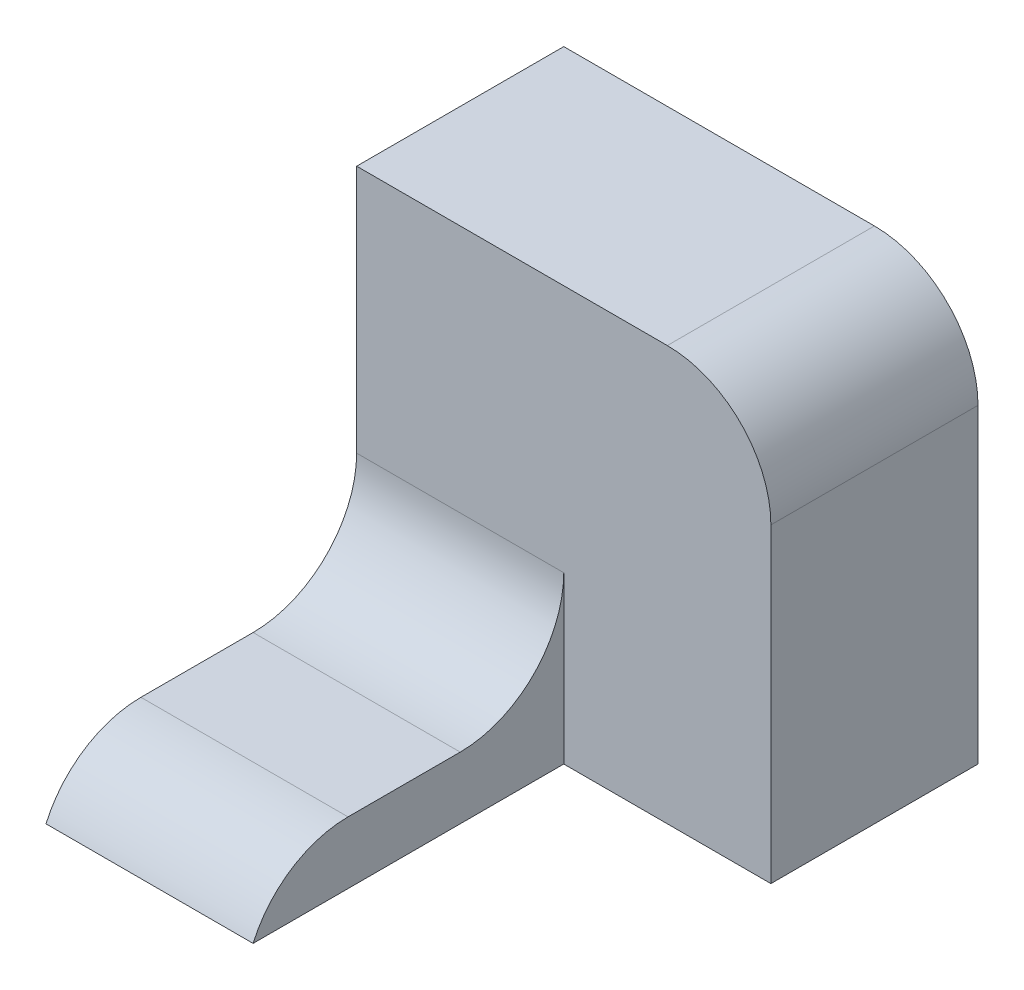
SolidWorks part; units mm, degrees
ref_plane "Front Plane" through (0, 0, 0) normal (0, 0, 1) x (1, 0, 0)
ref_plane "Top Plane" through (0, 0, 0) normal (0, 1, 0) x (1, 0, 0)
ref_plane "Right Plane" through (0, 0, 0) normal (1, 0, 0) x (0, 0, -1)
sketch "Sketch1" plane through (0, 0, 0) normal (0, 0, 1) x (1, 0, 0)
  line L1 (-30, -6) -> (-10, -6)
  line L2 (-10, -6) -> (-10, 0)
  line L3 (-10, 0) -> (-30, 0)
  line L4 (-30, 0) -> (-30, -6)
  dimension "D1" = 20
  dimension "Width" = 6
extrude "Boss-Extrude1" add sketch "Sketch1" along normal blind 30
sketch "Sketch2" plane through (0, 0, 0) normal (0, 0, 1) x (1, 0, 0)
  line L1 (-30, -6) -> (10, -6)
  line L2 (10, -6) -> (10, 34)
  line L3 (10, 34) -> (-30, 34)
  line L4 (-30, 34) -> (-30, -6)
  dimension "D1" = 40
  dimension "Width" = 40
extrude "Boss-Extrude2" add sketch "Sketch2" against normal blind 20
fillet "Fillet1" radius 10 3 edges at (-20, 0, 0) (10, 34, -10) (-20, 0, 30)
